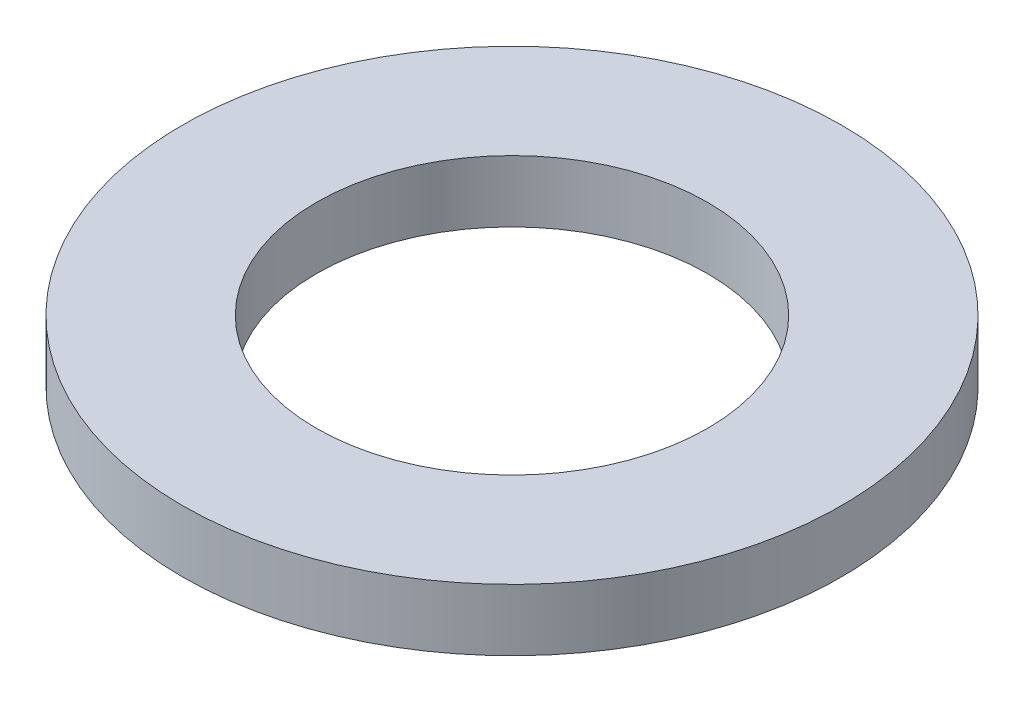
SolidWorks part; units mm, degrees
ref_plane "Front Plane" through (0, 0, 0) normal (0, 0, 1) x (1, 0, 0)
ref_plane "Top Plane" through (0, 0, 0) normal (0, 1, 0) x (1, 0, 0)
ref_plane "Right Plane" through (0, 0, 0) normal (1, 0, 0) x (0, 0, -1)
sketch "Sketch1" plane through (0, 0, 0) normal (0, 1, 0) x (1, 0, 0)
  circle A0 centre (0, 0) radius 80
  dimension "FLANGE_OD" = 160
extrude "Boss-Extrude1" add sketch "Sketch1" along normal blind 15
sketch "Sketch2" plane through (0, 0, 0) normal (0, 1, 0) x (1, 0, 0)
  circle A0 centre (0, 0) radius 47.5
  dimension "BORE_D" = 95
extrude "Cut-Extrude1" cut sketch "Sketch2" along normal through all
sketch "Sketch3" plane through (0, 15, 0) normal (0, 1, 0) x (1, 0, 0)
  circle A0 centre (0, 0) radius 32.6817 construction
  circle A1 centre (-32.6817, 0) radius 4.9115
  dimension "BOLT_D" = 9.823
  dimension "BOLT_PCD" = 65.3635
extrude "Cut-Extrude2" cut sketch "Sketch3" against normal blind 10.8364 rebuild error yes
pattern_circular "CirPattern1" count 6 over 360 rebuild error yes
